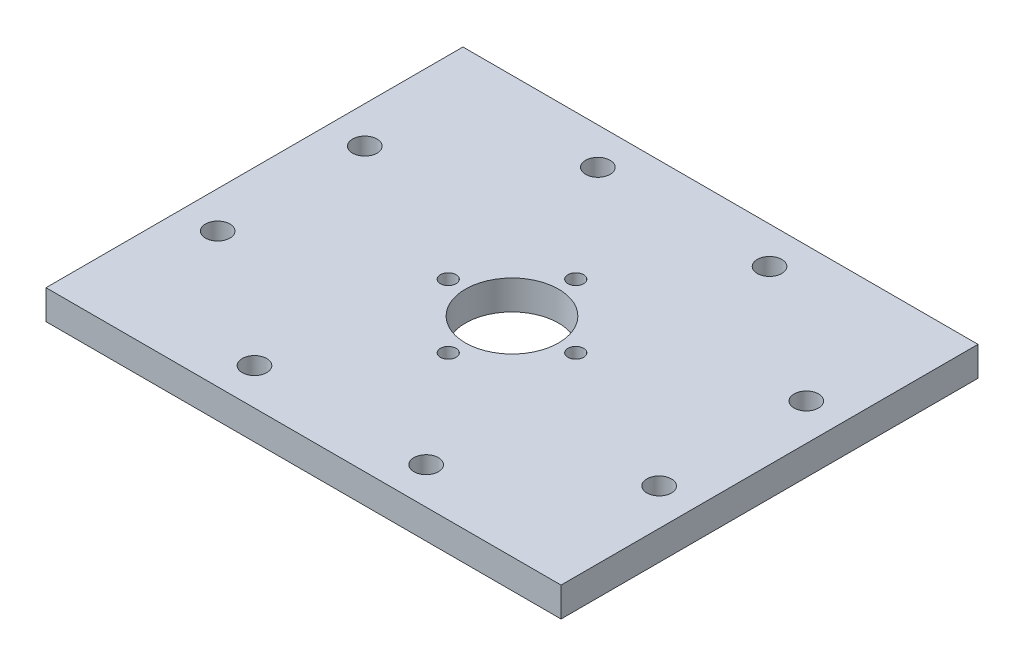
SolidWorks part; units mm, degrees
ref_plane "Front Plane" through (0, 0, 0) normal (0, 0, 1) x (1, 0, 0)
ref_plane "Top Plane" through (0, 0, 0) normal (0, 1, 0) x (1, 0, 0)
ref_plane "Right Plane" through (0, 0, 0) normal (1, 0, 0) x (0, 0, -1)
sketch "Sketch1" plane through (0, 0, 0) normal (0, 1, 0) x (1, 0, 0)
  line L0 (0, -3.3) -> (0, 3.3) construction
  line L1 (-52.5, 42.5) -> (52.5, 42.5)
  line L2 (-52.5, 42.5) -> (-52.5, -42.5)
  line L3 (-52.5, -42.5) -> (52.5, -42.5)
  line L4 (52.5, 42.5) -> (52.5, -42.5)
  line L5 (-52.5, 42.5) -> (52.5, -42.5) construction
  line L6 (-52.5, -42.5) -> (52.5, 42.5) construction
  line L7 (-3.3, 0) -> (3.3, 0) construction
  circle A0 centre (0, 0) radius 13 construction
  circle A1 centre (0, 13) radius 1.5 construction
  circle A2 centre (13, 0) radius 1.5 construction
  circle A3 centre (0, -13) radius 1.5 construction
  circle A4 centre (-13, 0) radius 1.5 construction
  circle A7 centre (0, 0) radius 9.5
  circle A8 centre (-17.5, 35) radius 2.5
  circle A9 centre (17.5, 35) radius 2.5
  circle A10 centre (17.5, -35) radius 2.5
  circle A11 centre (-17.5, -35) radius 2.5
  circle A12 centre (-45, 15) radius 2.5
  circle A13 centre (-45, -15) radius 2.5
  circle A14 centre (45, -15) radius 2.5
  circle A15 centre (45, 15) radius 2.5
  dimension "D1" = 26
  dimension "D2" = 3
  dimension "D4" = 19
  dimension "D7" = 5
  dimension "D10" = 5
  dimension "D5" = 17.5
  dimension "D6" = 105
  dimension "D8" = 85
  dimension "D9" = 35
  dimension "D11" = 45
  dimension "D12" = 15
  dimension "D3" = 4
extrude "Boss-Extrude1" add sketch "Sketch1" along normal blind 6
hole_wizard "CSK for M3 Flat Head Machine Screw1" positions "Sketch7" profile "Sketch8" countersink size "M3" standard "ANSI Metric" end condition through all
sketch "Sketch7" plane through (0, 0, 0) normal (0, -1, 0) x (-1, 0, 0)
  point P0 (-13, 0)
  point P3 (0, -13)
  point P6 (13, 0)
  point P9 (0, 13)
sketch "Sketch8" plane through (13, 0, 0) normal (1, 0, 0) x (0, 0, -1)
  line L0 (0, 0) -> (0, 6)
  line L1 (0, 6) -> (1.6, 6)
  line L2 (1.6, 6) -> (1.6, 1.55)
  line L3 (1.6, 1.55) -> (3.15, 0)
  line L5 (3.15, 0) -> (0, 0)
  line L6 (-1.6, 1.55) -> (-3.15, 0) construction
  line L11 (0, -6.35) -> (0, 107.95) construction
  dimension "Thru Hole Dia." = 3.2
  dimension "Thru Hole Depth" = 6
  dimension "Near C'Sink Dia." = 6.3
  dimension "Near C'Sink Angle" = 90
sketch "Sketch9" plane through (0, 0, 0) normal (0, 1, 0) x (1, 0, 0)
  line L0 (0, -3.3) -> (0, 3.3) construction
  line L1 (-3.3, 0) -> (3.3, 0) construction
  circle A0 centre (17.5, 35) radius 6
  circle A1 centre (-17.5, 35) radius 6
  circle A2 centre (-17.5, -35) radius 6
  circle A3 centre (17.5, -35) radius 6
  dimension "D1" = 12
equation "\"testbed_height\" = 91.50mm"
equation "\"plate_thickness\" = 6mm"
equation "\"main_body_splay_length\" = 48.5mm"
equation "\"splay_shaft_length_no_wires\" = 10mm"
equation "\"splay_shaft_length_wires\" = 6.5mm"
equation "\"timing_pulley_offset\" = 0mm"
equation "\"effective_motor_length\" = \"timing_pulley_offset\" + \"splay_shaft_length_no_wires\" + \"main_body_splay_length\""
equation "\"80_20_side\" = 25.4mm"
equation "\"80_20_length\" = 152.4mm"
equation "\"80_20_optic_mount_length\" = \"80_20_length\" - 25.4mm"
equation "\"optic_board_hole_size\" = 6.35mm"
equation "\"total_mounting_length\" = \"testbed_height\" - \"effective_motor_length\" - \"80_20_side\""
equation "\"mounting_vertical_portion_height\" = \"total_mounting_length\" - 2 * \"plate_thickness\""
equation "\"face_mount_width\" = 15.25mm"
equation "\"center_dist_to_face_mount_vertical_screws\" = 5mm"
equation "\"D1@Boss-Extrude1\"=\"plate_thickness\""
